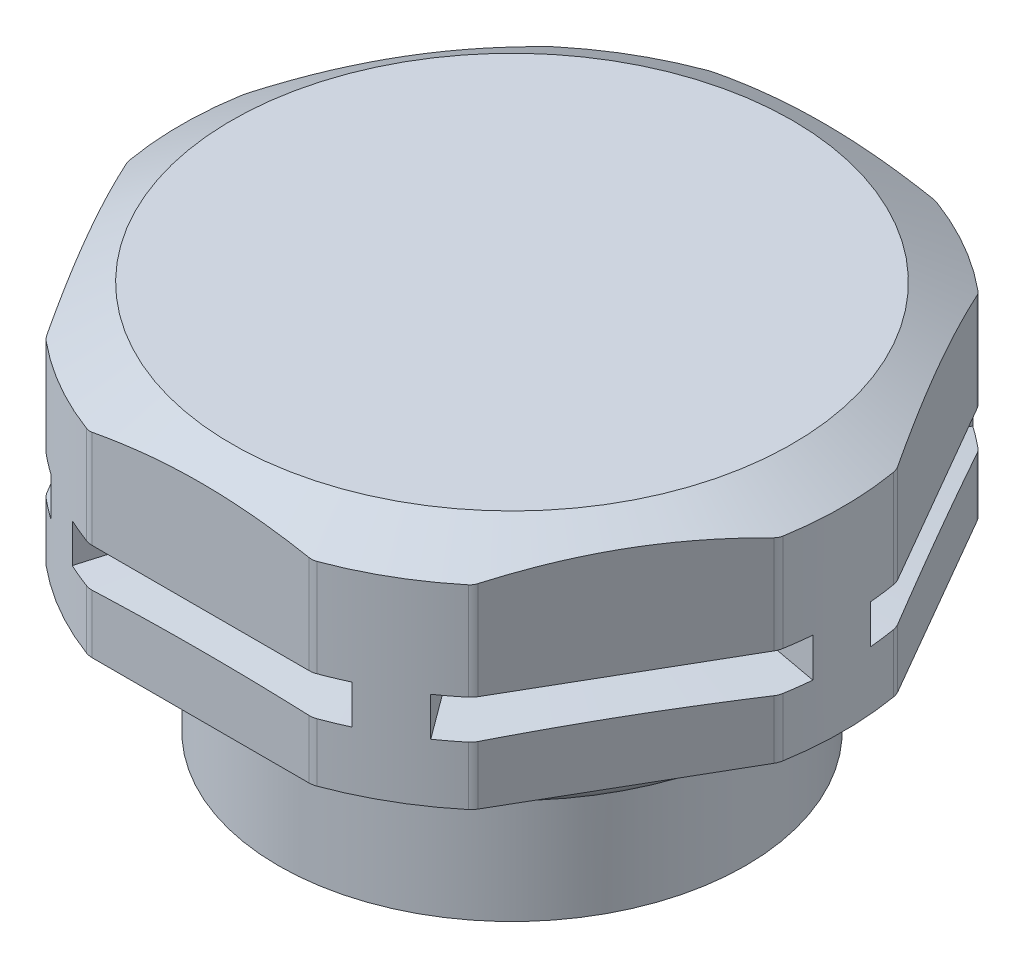
SolidWorks part; units mm, degrees
material "ABS"
ref_plane "Front" through (0, 0, 0) normal (0, 0, 1) x (1, 0, 0)
ref_plane "Top" through (0, 0, 0) normal (0, 1, 0) x (1, 0, 0)
ref_plane "Right" through (0, 0, 0) normal (1, 0, 0) x (0, 0, -1)
sketch "Sketch1" plane through (0, 0, 0) normal (0, 1, 0) x (1, 0, 0)
  line L1 (-4.6188, 8) -> (-9.2376, 0)
  line L2 (-9.2376, 0) -> (-4.6188, -8)
  line L3 (-4.6188, -8) -> (4.6188, -8)
  line L4 (4.6188, -8) -> (9.2376, 0)
  line L5 (9.2376, 0) -> (4.6188, 8)
  line L6 (4.6188, 8) -> (-4.6188, 8)
  circle A0 centre (0, 0) radius 8 construction
  circle A1 centre (0, 0) radius 8.5
  dimension "D2" = 17
  dimension "D1" = 16
extrude "Boss-Extrude1" add sketch "Sketch1" along normal blind 5.75 contours L3 A1 L4 L5 L6 L1 L2 region at (0, 0, 0)
sketch "Sketch2" plane through (0, 0, 0) normal (1, 0, 0) x (0, 0, -1)
  line L0 (-6, -1.1) -> (-5.25, -1.1)
  line L3 (-6, -1.1) -> (-6, -5.1)
  line L4 (-6, -5.1) -> (0, -5.1)
  line L5 (0, 0) -> (0, -5.1) construction
  line L6 (0, -5.1) -> (0, 0)
  line L7 (0, 0) -> (-5.25, 0)
  line L8 (-5.25, -1.1) -> (-5.25, 0)
  line L9 (-6.4875, 0) -> (-1.5125, 0) construction
  dimension "D2" = 1.1
  dimension "D1" = 12
  dimension "D4" = 4
  dimension "D5" = 0.75
revolve "Revolve1 M12x1 thread" add sketch "Sketch2" angle 360 about L5
cosmetic thread "Cosmetic Thread1" parameters "D2"=11
fillet "Fillet1" radius 0.5 12 edges at (2.8723, 2.875, -8) (-2.8723, 2.875, -8) (-5.4921, 2.875, -6.4875) (-8.3643, 2.875, -1.5125) (-8.3643, 2.875, 1.5125) (-5.4921, 2.875, 6.4875) (-2.8723, 2.875, 8) (2.8723, 2.875, 8) (5.4921, 2.875, -6.4875) (8.3643, 2.875, -1.5125) (8.3643, 2.875, 1.5125) (5.4921, 2.875, 6.4875)
sketch "Sketch3" plane through (0, 0, 0) normal (0, 0, 1) x (1, 0, 0)
  line L0 (7.201, 5.75) -> (8.5, 5)
  line L1 (8.5, 0) -> (8.5, 5.75) construction
  line L5 (0, 0) -> (0, 5.75) construction
  line L8 (8.5, 5) -> (8.5, 5.75)
  line L9 (8.5, 5.75) -> (7.201, 5.75)
  dimension "D1" = 30
  dimension "D2" = 1.5
revolve "Cut-Revolve2" cut sketch "Sketch3" angle 360 about L5
sketch "Sketch4" plane through (0, 0, 0) normal (1, 0, 0) x (0, 0, -1)
  line L0 (6, -1.1) -> (-6, -1.1) construction
  line L3 (0, 0) -> (0, -5.1) construction
  line L4 (-6, -5.1) -> (6, -5.1) construction
  line L5 (-6.4109, 0) -> (-1.5891, 0) construction
  circle A0 centre (-6.45, -0.55) radius 0.55
  point P13 (-7, -0.55)
  dimension "D1" = 14
revolve "Revolve2" add sketch "Sketch4" angle 360 about L3
sketch "Sketch7" plane through (0, 0, 0) normal (1, 0, 0) x (0, 0, -1)
  line L0 (-3.45, -5.1) -> (-3.45, -2.4024)
  line L1 (-6, -5.1) -> (6, -5.1) construction
  line L2 (-3.2825, -1.8483) -> (-2, 0.0786)
  line L3 (0, 0) -> (0, -1.2525) construction
  line L4 (0, 1.15) -> (0, -5.1)
  line L5 (0, -5.1) -> (-3.45, -5.1)
  line L8 (0, 1.65) -> (-3, 1.65)
  line L9 (0, 1.65) -> (0, 3.15)
  line L10 (0, 3.15) -> (-3, 3.15)
  line L11 (-3, 1.65) -> (-3, 3.15)
  arc A0 (0, 1.15) -> (-2, 0.0786) centre (0, -1.2525) ccw
  arc A1 (-3.45, -2.4024) -> (-3.2825, -1.8483) centre (-2.45, -2.4024) cw
  point P13 (-3.45, -2.1)
  dimension "D5" = 1
  dimension "D1" = 6.25
  dimension "D2" = 3.45
  dimension "D3" = 3
  dimension "D4" = 2
  dimension "D6" = 1.5
  dimension "D7" = 3
  dimension "D8" = 0.5
revolve "Cut-Revolve6" cut sketch "Sketch7" angle 360 about L3 region at (0, -2.4198, 1.5337) region at (0, 2.4, 1.5)
sketch "Sketch5" plane through (0, 0, 0) normal (-1, 0, 0) x (0, 0, 1)
  line L0 (-8.5, 1.5) -> (-0.5, 2.45)
  line L2 (-0.5, 2.5) -> (-8.5, 2.5)
  line L4 (-0.5, 2.5) -> (-0.5, 2.45)
  line L5 (1.5891, 0) -> (6.4109, 0) construction
  line L6 (0, 0) -> (0, 2.5) construction
  line L7 (-8.5, 2.5) -> (-8.5, 1.5)
  dimension "D1" = 1.5
  dimension "D2" = 1
  dimension "D3" = 1
  dimension "D4" = 0.05
  dimension "D5" = 8.5
revolve "Cut-Revolve5" cut sketch "Sketch5" angle 50 mid plane about L6
pattern_circular "CirPattern1" count 6 over 360 about axis through (0, 0, 0) along (0, 1, 0) of "Cut-Revolve5"
chamfer "Chamfer1" distance 1.5 angle 30 1 edges at (0, -5.1, 6) first distance on face at (0, -5.1, 6)
sketch "Sketch8" plane through (0, 5.75, 0) normal (0, 1, 0) x (1, 0, 0)
  line L0 (0, 1.75) -> (0, 0) construction
  line L1 (0, 0) -> (1.5155, -0.875) construction
  line L2 (1.2928, -1.1794) -> (0, -0.433)
  line L3 (1.6678, -0.5299) -> (0.375, 0.2165)
  line L4 (-1.6678, -0.5299) -> (-0.375, 0.2165)
  line L5 (-1.2928, -1.1794) -> (0, -0.433)
  line L6 (-0.375, 0.2165) -> (-0.375, 1.7093)
  line L7 (0.375, 0.2165) -> (0.375, 1.7093)
  circle A1 centre (0, 0) radius 1.75
  dimension "D2" = 120
  dimension "D3" = 3.5
  dimension "D1" = 0.75
extrude "Cut-Extrude1" cut sketch "Sketch8" against normal through all from surface contours L6 A1 L4 | L5 A1 L2 | L3 A1 L7 region at (0, 5.75, 1.1777) region at (1.0199, 5.75, -0.5888) region at (-1.0199, 5.75, -0.5888) starting at face at (0, 3.15, 3)
fillet "Fillet2" radius 0.25 9 edges at (1.2928, 1.0218, 1.1794) (0, 1.3803, 0.433) (-1.2928, 1.0218, 1.1794) (0.375, 1.3803, -0.2165) (-1.6678, 1.0218, 0.5299) (-0.375, 1.3803, -0.2165) (1.6678, 1.0218, 0.5299) (-0.375, 1.0218, -1.7093) (0.375, 1.0218, -1.7093)
